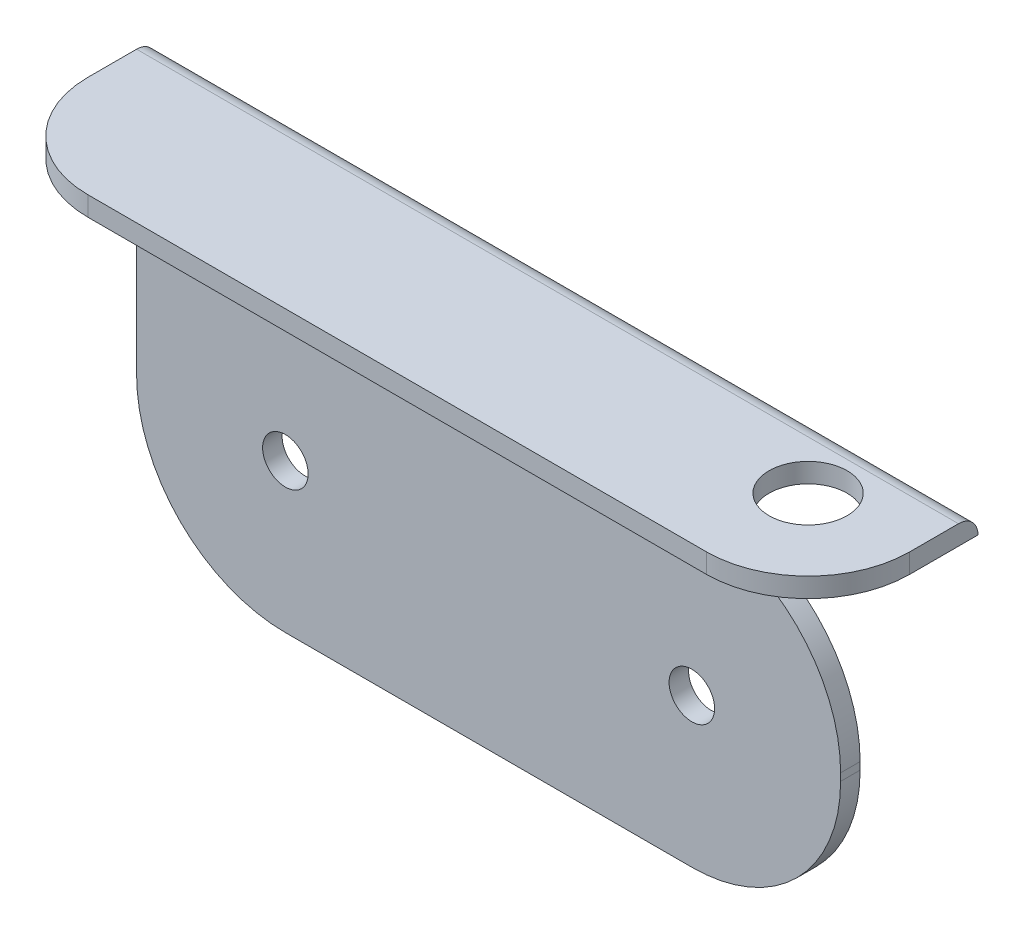
SolidWorks part; units mm, degrees
ref_plane "Front Plane" through (0, 0, 0) normal (0, 0, 1) x (1, 0, 0)
ref_plane "Top Plane" through (0, 0, 0) normal (0, 1, 0) x (1, 0, 0)
ref_plane "Right Plane" through (0, 0, 0) normal (1, 0, 0) x (0, 0, -1)
sketch "Sketch1" plane through (0, 0, 0) normal (0, 0, 1) x (1, 0, 0)
  line L0 (28.7655, 17.1437) -> (28.7655, -21.3844) construction
  line L1 (27.4955, 11.6205) -> (36.703, 20.5105)
  line L2 (36.703, 20.5105) -> (36.703, 22.0345)
  line L4 (-27.4955, 7.4295) -> (-27.4955, -11.6205)
  line L5 (-27.4955, -11.6205) -> (27.4955, -11.6205)
  line L6 (27.4955, 11.6205) -> (27.4955, -11.6205)
  line L7 (36.703, 22.0345) -> (-27.4955, 22.0345)
  line L8 (-27.4955, 22.0345) -> (-27.4955, 7.4295)
  line L9 (0, 27.93) -> (0, -27.9681) construction
  circle A0 centre (15.875, 0) radius 1.778
  circle A1 centre (-15.875, 0) radius 1.778
  point P5 (0, 0)
  point P15 (0, 0)
  point P18 (33.8274, 17.9705)
  dimension "D6" = 3.556
  dimension "D7" = 3.556
  dimension "D2" = 11.6205
  dimension "D3" = 2.54
  dimension "D4" = 1.524
  dimension "D5" = 31.75
  dimension "D8" = 11.6205
  dimension "D9" = 11.6205
  dimension "D10" = 11.6205
  dimension "D11" = 8.89
  dimension "D12" = 7.9375
extrude "Boss-Extrude1" add sketch "Sketch1" along normal blind 1.524
sketch "Sketch2" plane through (0, 0, 1.524) normal (0, 0, 1) x (1, 0, 0)
  line L1 (36.703, 22.0345) -> (17.653, 22.0345)
  line L2 (36.703, 22.0345) -> (36.703, 20.5105)
  line L3 (36.703, 20.5105) -> (17.653, 20.5105)
  line L4 (17.653, 22.0345) -> (17.653, 20.5105)
  point P5 (38.2905, 17.9705)
  dimension "D1" = 19.05
extrude "Boss-Extrude2" add sketch "Sketch2" along normal blind 11.7475
sketch "Sketch3" plane through (0, 20.5105, 0) normal (0, -1, 0) x (1, 0, 0)
  line L0 (27.4955, 1.524) -> (27.4955, 0) construction
  line L1 (17.653, 1.524) -> (36.703, 1.524) construction
  circle A0 centre (28.7655, 5.334) radius 3.048
  point P4 (28.7655, 6.1849)
  dimension "D2" = 6.096
  dimension "D1" = 1.27
  dimension "D3" = 3.81
extrude "Cut-Extrude2" cut sketch "Sketch3" against normal blind 13.9446
sketch "Sketch4" plane through (0, 0, 0) normal (0, 0, -1) x (-1, 0, 0)
  line L0 (-27.4955, -11.6205) -> (-27.4955, 11.6205) construction
  line L1 (-19.8755, 11.6205) -> (-36.703, 11.6205)
  line L2 (-17.3355, 14.1605) -> (-17.3355, 17.9705)
  line L3 (-19.8755, 20.5105) -> (-36.703, 20.5105)
  line L4 (-36.703, 11.6205) -> (-36.703, 20.5105)
  arc A0 (-19.8755, 11.6205) -> (-17.3355, 14.1605) centre (-19.8755, 14.1605) ccw
  arc A1 (-17.3355, 17.9705) -> (-19.8755, 20.5105) centre (-19.8755, 17.9705) ccw
  point P6 (-27.4955, 11.6205)
  point P11 (-17.9496, 12.3134)
  point P13 (-17.3355, 16.0655)
  dimension "D1" = 2.54
  dimension "D2" = 10.16
extrude "Cut-Extrude3" cut sketch "Sketch4" against normal blind 13.9446
sketch "Sketch5" plane through (0, 0, 1.524) normal (0, 0, 1) x (1, 0, 0)
  line L1 (17.653, 20.5105) -> (-27.4955, 20.5105)
  line L2 (17.653, 20.5105) -> (17.653, 22.0345)
  line L3 (17.653, 22.0345) -> (-27.4955, 22.0345)
  line L4 (-27.4955, 20.5105) -> (-27.4955, 22.0345)
extrude "Boss-Extrude3" add sketch "Sketch5" along normal up to surface (11.7475 mm away) up to face at (27.178, 21.2725, 13.2715)
fillet "Fillet1" radius 7.9375 1 edges at (36.703, 21.2725, 13.2715)
fillet "Fillet3" radius 11.6205 1 edges at (27.4955, -11.6205, 0.762)
fillet "Fillet4" radius 11.6205 2 edges at (-27.4955, -11.6205, 0.762) (27.4955, 11.6205, 0.762)
fillet "Fillet5" radius 1.524 1 edges at (-3.81, 20.5105, 1.524)
fillet "Fillet6" radius 1.524 1 edges at (4.6038, 22.0345, 0)
fillet "Fillet7" radius 7.9375 1 edges at (-27.4955, 21.2725, 13.2715)
